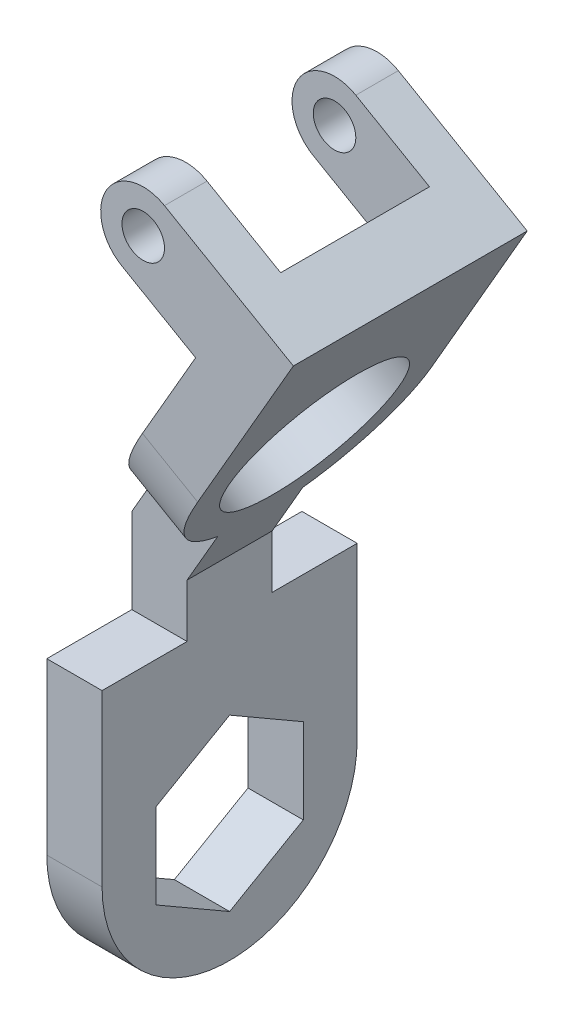
SolidWorks part; units mm, degrees
ref_plane "Front Plane" through (0, 0, 0) normal (0, 0, 1) x (1, 0, 0)
ref_plane "Top Plane" through (0, 0, 0) normal (0, 1, 0) x (1, 0, 0)
ref_plane "Right Plane" through (0, 0, 0) normal (1, 0, 0) x (0, 0, -1)
sketch "Sketch1" plane through (0, 0, 0) normal (1, 0, 0) x (0, 0, -1)
  line L0 (-38.1, 0) -> (-38.1, 50.8)
  line L1 (0, 25.4) -> (-21.997, 12.7)
  line L2 (-21.997, 12.7) -> (-21.997, -12.7)
  line L3 (-21.997, -12.7) -> (0, -25.4)
  line L4 (0, -25.4) -> (21.997, -12.7)
  line L5 (21.997, -12.7) -> (21.997, 12.7)
  line L6 (21.997, 12.7) -> (0, 25.4)
  line L7 (38.1, 0) -> (38.1, 50.8)
  line L8 (-38.1, 50.8) -> (-12.7, 50.8)
  line L9 (0, -38.1) -> (0, 76.2) construction
  line L10 (12.7, 76.2) -> (-12.7, 76.2)
  line L11 (-12.7, 76.2) -> (-12.7, 50.8)
  line L12 (12.7, 50.8) -> (38.1, 50.8)
  line L13 (12.7, 76.2) -> (12.7, 50.8)
  arc A0 (-38.1, 0) -> (38.1, 0) centre (0, 0) ccw
  circle A1 centre (0, 0) radius 21.997 construction
  dimension "D1" = 76.2
  dimension "D2" = 50.8
  dimension "D3" = 50.8
  dimension "D4" = 25.4
  dimension "D5" = 12.7
extrude "Boss-Extrude1" add sketch "Sketch1" along normal blind 16.51
ref_plane "Plane1" through (-32.9956, 19.05, 0) normal (0.866, -0.5, 0) x (0, 0, 1)
sketch "Sketch2" plane through (-32.9956, 19.05, 0) normal (0.866, -0.5, 0) x (0, 0, 1)
  line L0 (0, -65.9911) -> (0, -189.3247) construction
  line L1 (-12.7, -65.9911) -> (12.7, -65.9911) construction
  line L2 (-12.7, -65.9911) -> (12.7, -65.9911)
  line L3 (12.7, -65.9911) -> (12.7, -84.2571)
  line L4 (-12.7, -65.9911) -> (-12.7, -84.2571)
  line L5 (34.925, -116.7911) -> (34.925, -173.9411)
  line L6 (-34.925, -116.7911) -> (-34.925, -173.9411)
  line L7 (34.925, -173.9411) -> (-34.925, -173.9411)
  arc A0 (-12.7, -84.2571) -> (-34.925, -116.7911) centre (0, -116.7911) ccw
  circle A1 centre (0, -116.7911) radius 25.4
  arc A2 (34.925, -116.7911) -> (12.7, -84.2571) centre (0, -116.7911) ccw
  dimension "D2" = 69.85
  dimension "D3" = 50.8
  dimension "D1" = 50.8
  dimension "D4" = 57.15
extrude "Boss-Extrude2" add sketch "Sketch2" along normal blind 19.05
sketch "Sketch3" plane through (0, 0, 0) normal (0, 0, 1) x (1, 0, 0)
  line L0 (53.975, 169.6874) -> (31.978, 182.3874)
  line L2 (19.278, 160.3904) -> (41.275, 147.6904)
  line L3 (53.975, 169.6874) -> (25.4, 120.1941) construction
  line L4 (41.275, 147.6904) -> (53.975, 169.6874)
  line L5 (25.628, 171.3889) -> (47.625, 158.6889) construction
  line L6 (41.8978, 110.6691) -> (25.4, 120.1941) construction
  circle A0 centre (25.628, 171.3889) radius 6.35
  arc A1 (31.978, 182.3874) -> (19.278, 160.3904) centre (25.628, 171.3889) ccw
  dimension "D3" = 12.7
  dimension "D4" = 12.7
  dimension "D1" = 25.4
  dimension "D2" = 31.75
  dimension "D5" = 25.4
extrude "Boss-Extrude3" add sketch "Sketch3" along direction (0, 0, 1) on the side of the normal blind 34.925 and the other way blind 34.925
extrude "Cut-Extrude1" cut sketch "Sketch3<2>" against normal mid plane 44.45
sketch "Sketch3<2>" plane through (0, 0, 0) normal (0, 0, 1) x (1, 0, 0) same geometry as "Sketch3"
